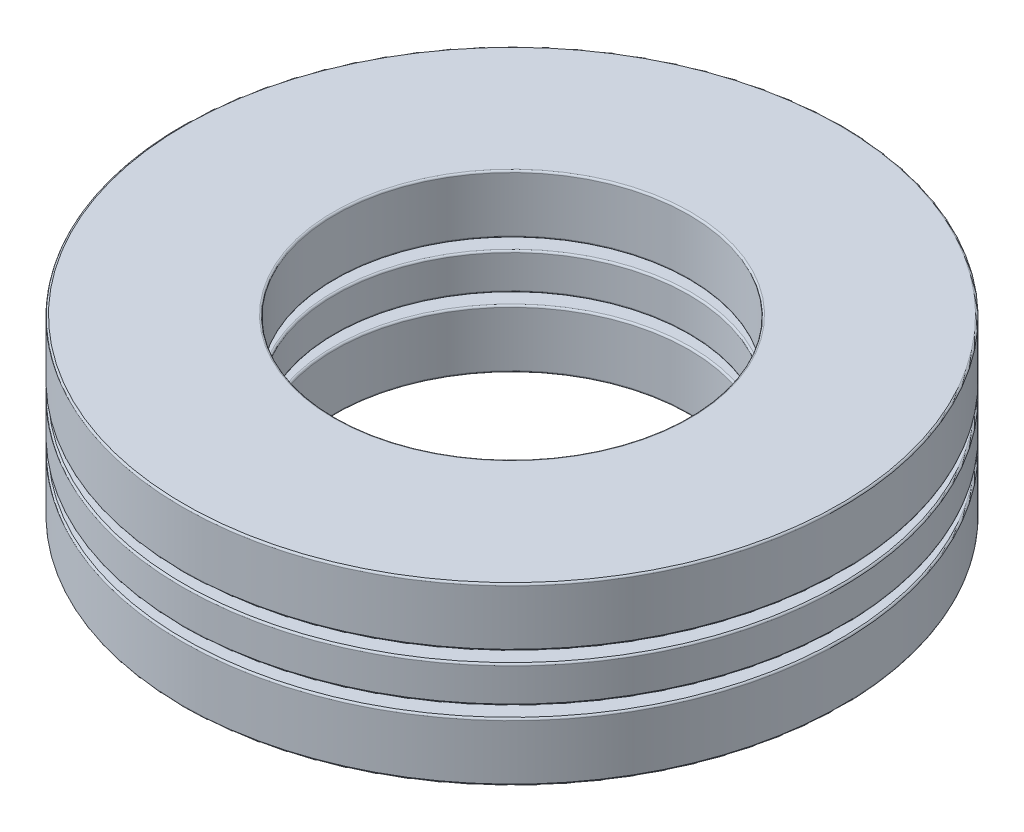
SolidWorks part; units mm, degrees
material "Plain Carbon Steel"
ref_plane "Front Plane" through (0, 0, 0) normal (0, 0, 1) x (1, 0, 0)
ref_plane "Top Plane" through (0, 0, 0) normal (0, 1, 0) x (1, 0, 0)
ref_plane "Right Plane" through (0, 0, 0) normal (1, 0, 0) x (0, 0, -1)
sketch "Sketch1" plane through (0, 0, 0) normal (1, 0, 0) x (0, 0, -1)
  line L0 (-11.9062, 0) -> (11.9062, 0) construction
  line L1 (0, -3.1623) -> (0, 3.1623) construction
  line L2 (-11.9062, 0.6588) -> (-6.3881, 0.6588)
  line L3 (-11.9062, 0.6588) -> (-11.9062, -0.6588)
  line L4 (-11.9062, -0.6588) -> (-6.3881, -0.6588)
  line L5 (-6.3881, 0.6588) -> (-6.3881, -0.6588)
  line L6 (-9.1472, 1.0541) -> (-9.1472, -1.0541) construction
  circle A0 centre (-9.1472, 0) radius 1.0541 construction
  point P13 (-9.1472, 0.6588)
  dimension "OD" = 23.8125
  dimension "Shaft Dia" = 12.7762
  dimension "Th" = 6.3246
  dimension "D1" = 2.1082
  dimension "D2" = 1.3176
revolve "Revolve1" add sketch "Sketch1" angle 360 about L1
sketch "Sketch3" plane through (0, 0, 0) normal (1, 0, 0) x (0, 0, -1)
  line L0 (-9.1472, 1.0541) -> (-9.1472, -1.0541)
  arc A0 (-9.1472, 1.0541) -> (-9.1472, -1.0541) centre (-9.1472, 0) ccw
  circle A1 centre (-9.1472, 0) radius 1.0541 construction
revolve "Cut-Revolve1" cut sketch "Sketch3" angle 360 about L0
sketch "Sketch2" plane through (0, 0, 0) normal (1, 0, 0) x (0, 0, -1)
  line L0 (-9.1472, 1.0541) -> (-9.1472, -1.0541)
  arc A0 (-9.1472, 1.0541) -> (-9.1472, -1.0541) centre (-9.1472, 0) ccw
  circle A2 centre (-9.1472, 0) radius 1.0541 construction
revolve "Revolve2" add sketch "Sketch2" angle 360 about L0
ref_axis "Axis1" through (0, 3.1623, 0) along (0, -1, 0)
pattern_circular "CirPattern1" count 5 every 72 about axis through (0, 3.1623, 0) along (0, -1, 0) of bodies 187
pattern_circular "CirPattern2" count 5 every 72 about axis through (0, 3.1623, 0) along (0, -1, 0) of "Cut-Revolve1"
sketch "Sketch4" plane through (0, 0, 0) normal (1, 0, 0) x (0, 0, -1)
  line L0 (-11.9062, 0.6588) -> (-11.9062, -0.6588) construction
  line L1 (-11.9062, 1.0541) -> (-6.3881, 1.0541)
  line L2 (-11.9062, 1.0541) -> (-11.9062, 3.1623)
  line L3 (-11.9062, 3.1623) -> (-6.3881, 3.1623)
  line L4 (-6.3881, 1.0541) -> (-6.3881, 3.1623)
  line L5 (-11.9062, -3.1623) -> (-6.3881, -3.1623)
  line L6 (-11.9062, -3.1623) -> (-11.9062, -1.0541)
  line L7 (-11.9062, -1.0541) -> (-6.3881, -1.0541)
  line L8 (-6.3881, -3.1623) -> (-6.3881, -1.0541)
  line L9 (-9.1472, 1.0541) -> (-9.1472, -1.0541) construction
  line L10 (-6.3881, 0.6588) -> (-6.3881, -0.6588) construction
  line L11 (0, 0) -> (-11.9062, 0) construction
  line L12 (-11.9062, 0) -> (11.9062, 0) construction
  dimension "Ht" = 6.3246
revolve "Revolve3" add sketch "Sketch4" angle 360 about L1
fillet "Fillet1" radius 0.0632 4 edges at (0, 1.0541, -6.3881) (0, 3.1623, -6.3881) (0, 1.0541, -11.9062) (0, 3.1623, -11.9062)
fillet "Fillet2" radius 0.0632 4 edges at (0, -0.6588, -6.3881) (0, 0.6588, -6.3881) (0, -0.6588, -11.9062) (0, 0.6588, -11.9062)
fillet "Fillet3" radius 0.0632 4 edges at (0, -3.1623, -6.3881) (0, -1.0541, -6.3881) (0, -3.1623, -11.9062) (0, -1.0541, -11.9062)
equation "\"D1@Sketch1\" = \"Th@Sketch1\"/3"
equation "\"D2@Sketch1\" = \"D1@Sketch1\"*.625"
equation "\"Balls@CirPattern1\" = \"OD@Sketch1\"*5"
equation "\"Angle@CirPattern1\" = 360/\"Balls@CirPattern1\""
equation "\"D1@CirPattern2\" = \"Balls@CirPattern1\""
equation "\"D2@CirPattern2\" = \"Angle@CirPattern1\""
equation "\"D1@Fillet1\" = \"Th@Sketch1\"*.01"
equation "\"D1@Fillet2\" = \"D1@Fillet1\""
equation "\"D1@Fillet3\" = \"D1@Fillet1\""
